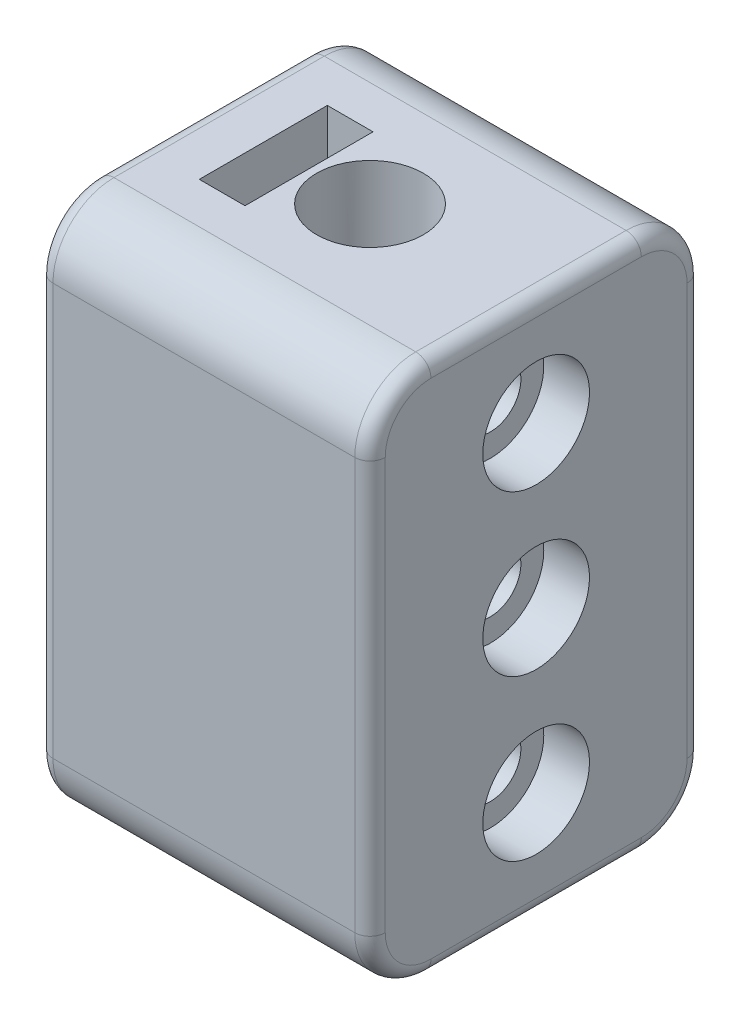
SolidWorks part; units mm, degrees
ref_plane "Alzado" through (0, 0, 0) normal (0, 0, 1) x (1, 0, 0)
ref_plane "Planta" through (0, 0, 0) normal (0, 1, 0) x (1, 0, 0)
ref_plane "Vista lateral" through (0, 0, 0) normal (1, 0, 0) x (0, 0, -1)
sketch "Croquis1" plane through (0, 0, 0) normal (1, 0, 0) x (0, 0, -1)
  line L1 (0, 0) -> (-21.8, 0)
  line L2 (0, 0) -> (0, -35)
  line L3 (0, -35) -> (-21.8, -35)
  line L4 (-21.8, 0) -> (-21.8, -35)
  dimension "D1" = 21.8
  dimension "D2" = 35
extrude "Saliente-Extruir1" add sketch "Croquis1" along normal blind 21.8 contours L2 L3 L4 L1
sketch "Croquis6" plane through (0, 0, 0) normal (-1, 0, 0) x (0, 0, 1)
  line L0 (10.9, -28) -> (10.9, -35) construction
  line L1 (0, -17.5) -> (2.4908, -17.5) construction
  line L2 (10.9, -28) -> (10.9, -17.5) construction
  line L3 (0, 0) -> (0, -35) construction
  circle A0 centre (10.9, -28) radius 2
  circle A1 centre (10.9, -17.5) radius 2
  circle A2 centre (10.9, -7) radius 2
  dimension "D1" = 10.5
  dimension "D3" = 4
  dimension "D4" = 4
  dimension "D2" = 7
extrude "Cortar-Extruir2" cut sketch "Croquis6" against normal up to surface (21.8 mm away) up to face at (21.8, -17.5, 10.9)
fillet "Redondeo2" radius 1 8 edges at (0, -35, 10.9) (21.8, -35, 10.9) (0, -17.5, 21.8) (21.8, -17.5, 21.8) (0, -17.5, 0) (21.8, -17.5, 0) (0, 0, 10.9) (21.8, 0, 10.9)
fillet "Redondeo3" radius 4 12 edges at (0.2929, -0.2929, 21.5071) (21.5071, -0.2929, 21.5071) (10.9, 0, 21.8) (0.2929, -0.2929, 0.2929) (21.5071, -0.2929, 0.2929) (10.9, 0, 0) (0.2929, -34.7071, 0.2929) (21.5071, -34.7071, 0.2929) (0.2929, -34.7071, 21.5071) (21.5071, -34.7071, 21.5071) (10.9, -35, 21.8) (10.9, -35, 0)
sketch "Croquis7" plane through (21.8, 0, 0) normal (1, 0, 0) x (0, 0, -1)
  line L0 (-20.8, -17.5) -> (-16.9958, -17.5) construction
  line L1 (-20.8, -4) -> (-20.8, -31) construction
  line L2 (-10.9, -28) -> (-10.9, -17.5) construction
  line L3 (-10.9, -17.5) -> (-10.9, -7) construction
  circle A0 centre (-10.9, -28) radius 3.5
  circle A1 centre (-10.9, -17.5) radius 3.5
  circle A2 centre (-10.9, -7) radius 3.5
  dimension "D1" = 7
  dimension "D2" = 7
  dimension "D3" = 10.5
extrude "Cortar-Extruir3" cut sketch "Croquis7" against normal blind 3
sketch "Croquis11" plane through (0, -35, 0) normal (0, -1, 0) x (1, 0, 0)
  line L0 (10.9, 4) -> (10.9, 10.9) construction
  line L1 (1, 4) -> (20.8, 4) construction
  line L2 (14.9, 10.9) -> (10.9, 10.9) construction
  line L3 (6.9, 15.1) -> (6.9, 6.7)
  line L4 (3.9, 15.1) -> (6.9, 15.1)
  line L5 (3.9, 6.7) -> (3.9, 15.1)
  line L6 (6.9, 6.7) -> (3.9, 6.7)
  line L10 (14.9, 6.7) -> (17.9, 6.7)
  line L11 (17.9, 6.7) -> (17.9, 15.1)
  line L12 (17.9, 15.1) -> (14.9, 15.1)
  line L13 (14.9, 15.1) -> (14.9, 6.7)
  circle A1 centre (10.9, 10.9) radius 3.5
  dimension "D1" = 4
extrude "Cortar-Extruir4" cut sketch "Croquis11" against normal up to next
pattern_linear "MatrizL1" count 2 spacing 18.8 along (-1, 0, 0) of "Cortar-Extruir3"
sketch "Croquis14" plane through (0, 0, 0) normal (0, 1, 0) x (1, 0, 0)
  line L0 (14.9, -15.1) -> (17.9, -15.1) construction
  line L1 (17.9, -15.1) -> (17.9, -6.7) construction
  line L2 (17.9, -6.7) -> (14.9, -6.7) construction
  line L3 (14.9, -6.7) -> (14.9, -15.1) construction
  line L4 (14.9, -15.1) -> (17.9, -15.1)
  line L5 (17.9, -15.1) -> (17.9, -6.7)
  line L6 (17.9, -6.7) -> (14.9, -6.7)
  line L7 (14.9, -6.7) -> (14.9, -15.1)
extrude "Saliente-Extruir2" add sketch "Croquis14" against normal blind 20
sketch "Croquis15" plane through (0, -35, 0) normal (0, -1, 0) x (1, 0, 0)
  line L0 (3.9, 6.7) -> (6.9, 6.7) construction
  line L1 (6.9, 6.7) -> (6.9, 15.1) construction
  line L2 (3.9, 15.1) -> (3.9, 6.7) construction
  line L3 (6.9, 15.1) -> (3.9, 15.1) construction
  line L4 (3.9, 6.7) -> (6.9, 6.7)
  line L5 (6.9, 6.7) -> (6.9, 15.1)
  line L6 (3.9, 15.1) -> (3.9, 6.7)
  line L7 (6.9, 15.1) -> (3.9, 15.1)
extrude "Saliente-Extruir3" add sketch "Croquis15" against normal blind 20
